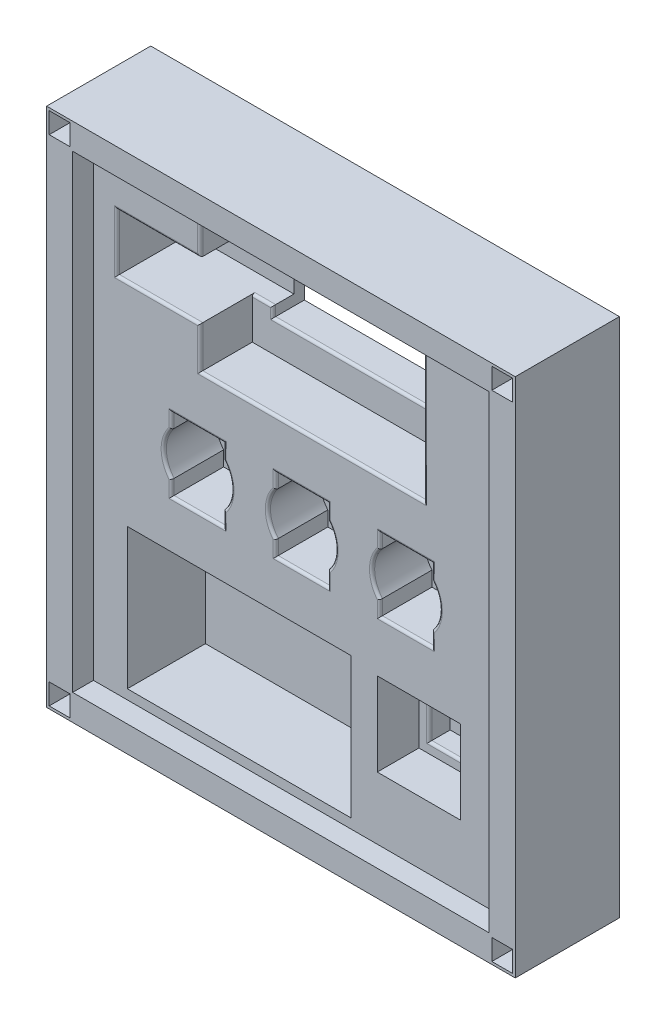
SolidWorks part; units mm, degrees
ref_plane "Front Plane" through (0, 0, 0) normal (0, 0, 1) x (1, 0, 0)
ref_plane "Top Plane" through (0, 0, 0) normal (0, 1, 0) x (1, 0, 0)
ref_plane "Right Plane" through (0, 0, 0) normal (1, 0, 0) x (0, 0, -1)
sketch "Sketch2" plane through (0, 0, 0) normal (0, 0, 1) x (1, 0, 0)
  line L1 (-45, 50) -> (45, 50)
  line L2 (-45, 50) -> (-45, -50)
  line L3 (-45, -50) -> (45, -50)
  line L4 (45, 50) -> (45, -50)
  line L5 (-45, 50) -> (45, -50) construction
  line L6 (-45, -50) -> (45, 50) construction
  point P0 (0, 0)
  dimension "D1" = 90
  dimension "D2" = 100
extrude "Boss-Extrude1" add sketch "Sketch2" along normal blind 50 contours L2 L1 L4 L3
sketch "Sketch4" plane through (0, 0, 0) normal (0, 0, -1) x (-1, 0, 0)
  line L0 (-45, 50) -> (45, 50)
  line L1 (45, 50) -> (45, -50)
  line L2 (45, -50) -> (-45, -50)
  line L3 (-45, -50) -> (-45, 50)
  line L4 (0, 0) -> (0, 30)
  line L5 (0, 0) -> (45, 0)
  line L6 (45, 0) -> (-45, 0)
  line L7 (0, 0) -> (0, -50)
  line L8 (0, -50) -> (0, -25)
  line L9 (0, -25) -> (0, 0)
  line L10 (0, 0) -> (0, 30)
  line L11 (-15.5, 22.5) -> (-23.5, 22.5)
  line L12 (-15.5, 37.5) -> (15.5, 37.5)
  line L13 (-15.5, 37.5) -> (-15.5, 22.5)
  line L14 (-15.5, 22.5) -> (15.5, 22.5)
  line L15 (15.5, 37.5) -> (15.5, 22.5)
  line L16 (-15.5, 37.5) -> (15.5, 22.5) construction
  line L17 (-15.5, 22.5) -> (15.5, 37.5) construction
  line L18 (-23.5, 22.5) -> (-23.5, 16.5)
  line L19 (-23.5, 16.5) -> (19.5, 16.5)
  line L20 (19.5, 16.5) -> (19.5, 41.5)
  line L21 (19.5, 41.5) -> (-23.5, 41.5)
  line L22 (-23.5, 41.5) -> (-23.5, 22.5)
  line L23 (15.5, 30) -> (15.5, 35.5)
  line L24 (15.5, 35.5) -> (35.5, 35.5)
  line L25 (35.5, 35.5) -> (35.5, 24.5)
  line L26 (35.5, 24.5) -> (15.5, 24.5)
  line L27 (0, 0) -> (20, 0)
  line L28 (0, 0) -> (-20, 0)
  line L34 (22.5, -25) -> (22.5, -22)
  line L35 (22.5, -22) -> (32.5, -22)
  line L39 (0, 0) -> (5, 0)
  line L40 (5, 0) -> (5, -7)
  line L41 (5, -7) -> (-5, -7)
  line L42 (-5, -7) -> (-5, 7)
  line L43 (-5, 7) -> (5, 7)
  line L44 (5, 7) -> (5, 0)
  line L45 (-20, 0) -> (-15, 0)
  line L46 (-15, 0) -> (-15, 7)
  line L47 (-15, 7) -> (-25, 7)
  line L48 (-25, 7) -> (-25, -7)
  line L49 (-25, -7) -> (-15, -7)
  line L50 (-15, -7) -> (-15, 0)
  line L51 (15, -7) -> (15, 0)
  line L52 (25, -7) -> (15, -7)
  line L53 (25, 7) -> (25, -7)
  line L54 (15, 7) -> (25, 7)
  line L55 (15, 0) -> (15, 7)
  line L56 (0, 0) -> (0, 15)
  line L57 (0, 15) -> (0, 7.5)
  line L58 (-45, -25) -> (45, -25)
  line L59 (0, -25) -> (22.5, -25)
  line L60 (0, -25) -> (-22.5, -25)
  line L61 (-22.5, -25) -> (-11.25, -25)
  line L62 (32.5, -22) -> (32.5, -28)
  line L63 (-16.5, -31) -> (-28.5, -31)
  line L64 (-28.5, -19) -> (-28.5, -31)
  line L65 (-16.5, -19) -> (-28.5, -19)
  line L66 (-16.5, -19) -> (-16.5, -31)
  line L67 (-14.5, -17) -> (-30.5, -17)
  line L68 (-30.5, -17) -> (-30.5, -33)
  line L69 (-14.5, -33) -> (-30.5, -33)
  line L70 (-14.5, -17) -> (-14.5, -33)
  line L71 (32.5, -28) -> (12.5, -28)
  line L72 (12.5, -28) -> (12.5, -22)
  line L73 (12.5, -22) -> (22.5, -22)
  line L74 (32.5, -25) -> (32.5, -17.1471)
  line L75 (32.5, -17.1471) -> (32.5, -42.1471)
  line L76 (32.5, -42.1471) -> (1.5, -42.1471)
  line L77 (1.5, -42.1471) -> (1.5, -17.1471)
  line L78 (1.5, -17.1471) -> (32.5, -17.1471)
  line L79 (33.5, -16.1471) -> (33.5, -43.1471)
  line L80 (33.5, -43.1471) -> (0.5, -43.1471)
  line L81 (0.5, -43.1471) -> (0.5, -16.1471)
  line L82 (0.5, -16.1471) -> (33.5, -16.1471)
  circle A0 centre (0, 0) radius 3.25
  circle A1 centre (-20, 0) radius 3.25
  circle A2 centre (20, 0) radius 3.25
  circle A4 centre (-22.5, -25) radius 4.5
  dimension "D3" = 1
  dimension "D1" = 15
  dimension "D2" = 31
  dimension "D6" = 30
  dimension "D7" = 0
  dimension "D8" = 25
  dimension "D9" = 22.5
sketch "Sketch5" plane through (0, 0, 50) normal (0, 0, 1) x (1, 0, 0)
  line L0 (-45, 50) -> (45, 50)
  line L1 (45, 50) -> (45, -50)
  line L2 (45, -50) -> (-45, -50)
  line L3 (-45, -50) -> (-45, 50)
  line L4 (-40, -45) -> (-40, 45)
  line L5 (-40, 45) -> (40, 45)
  line L6 (40, 45) -> (40, -45)
  line L7 (40, -45) -> (-40, -45)
  line L100 (-15.5, 37.5) -> (-15.5, 22.5)
  line L101 (-15.5, 22.5) -> (15.5, 22.5)
  line L102 (15.5, 22.5) -> (15.5, 37.5)
  line L103 (15.5, 37.5) -> (-15.5, 37.5)
  line L104 (-12.5, -22) -> (-32.5, -22)
  line L105 (-32.5, -22) -> (-32.5, -28)
  line L106 (-32.5, -28) -> (-12.5, -28)
  line L107 (-12.5, -28) -> (-12.5, -22)
  line L108 (-19.5, 41.5) -> (23.5, 41.5)
  line L109 (23.5, 41.5) -> (23.5, 16.5)
  line L110 (23.5, 16.5) -> (-19.5, 16.5)
  line L111 (-19.5, 16.5) -> (-19.5, 41.5)
  line L112 (-35.5, 35.5) -> (-15.5, 35.5)
  line L113 (-15.5, 35.5) -> (-15.5, 24.5)
  line L114 (-15.5, 24.5) -> (-35.5, 24.5)
  line L115 (-35.5, 24.5) -> (-35.5, 35.5)
  line L116 (-25, 7) -> (-15, 7)
  line L117 (-15, 7) -> (-15, -7)
  line L118 (-15, -7) -> (-25, -7)
  line L119 (-25, -7) -> (-25, 7)
  line L120 (-5, 7) -> (5, 7)
  line L121 (5, 7) -> (5, -7)
  line L122 (5, -7) -> (-5, -7)
  line L123 (-5, -7) -> (-5, 7)
  line L124 (15, 7) -> (25, 7)
  line L125 (25, 7) -> (25, -7)
  line L126 (25, -7) -> (15, -7)
  line L127 (15, -7) -> (15, 7)
  line L128 (-33.5, -16.1471) -> (-0.5, -16.1471)
  line L129 (-0.5, -16.1471) -> (-0.5, -43.1471)
  line L130 (-0.5, -43.1471) -> (-33.5, -43.1471)
  line L131 (-33.5, -43.1471) -> (-33.5, -16.1471)
  line L132 (16.5, -19) -> (28.5, -19)
  line L133 (28.5, -19) -> (28.5, -31)
  line L134 (28.5, -31) -> (16.5, -31)
  line L135 (16.5, -31) -> (16.5, -19)
  line L136 (14.5, -33) -> (14.5, -17)
  line L137 (14.5, -17) -> (30.5, -17)
  line L138 (30.5, -17) -> (30.5, -33)
  line L139 (30.5, -33) -> (14.5, -33)
  circle A40 centre (-20, 0) radius 3.25
  circle A41 centre (0, 0) radius 3.25
  circle A42 centre (20, 0) radius 3.25
  circle A43 centre (22.5, -25) radius 4.5
  circle A44 centre (-20, 0) radius 6.5
  circle A45 centre (0, 0) radius 6.5
  circle A46 centre (20, 0) radius 6.5
  line M9 (-45, -50) -> (45, -50)
  line M10 (45, -50) -> (45, 50)
  line M11 (45, 50) -> (-45, 50)
  line M12 (-45, 50) -> (-45, -50)
  dimension "D1" = 5
extrude "Cut-Extrude1" cut sketch "Sketch5" against normal blind 50 contours L102 L103 L100 L101 | A40 | A41 | L106 L107 L104 L105 | A42 | A43 region at (0, 30, 50) region at (-22.5, -25, 50) region at (-20, 0, 50) region at (0, 0, 50) region at (20, 0, 50) region at (22.5, -25, 50)
extrude "Cut-Extrude2" cut sketch "Sketch5<3>" against normal blind 44 contours L111 L110 L109 L108 L103 L102 L101 L100 region at (-15.9974, 36.5, 50)
sketch "Sketch5<3>" plane through (0, 0, 50) normal (0, 0, 1) x (1, 0, 0) same geometry as "Sketch5"
extrude "Cut-Extrude3" cut sketch "Sketch5<4>" against normal blind 48 contours L115 L114 L111 L112 | L114 L100 L112 L111 region at (-17.5, 30, 50) region at (-27.5, 30, 50)
sketch "Sketch5<4>" plane through (0, 0, 50) normal (0, 0, 1) x (1, 0, 0) same geometry as "Sketch5"
extrude "Cut-Extrude4" cut sketch "Sketch5<5>" against normal blind 44 contours L119 L118 L117 L116 A40 | L123 L122 L121 L120 A41 | L127 L126 L125 L124 A42 | L119 A44 | L117 A44 | L123 A45 | L121 A45 | L127 A46 | L125 A46 | A44 L117 L116 L119 | A44 L119 L118 L117 | A45 L123 L122 L121 | A45 L121 L120 L123 | A46 L125 L124 L127 | A46 L127 L126 L125 region at (-20, 6.896, 50) region at (-20, 6.336, 50) region at (-25.6064, 0, 50) region at (-14.3936, 0, 50) region at (-20, -6.604, 50) region at (0, 6.896, 50) region at (0, 6.336, 50) region at (-5.6064, 0, 50) region at (5.6064, 0, 50) region at (0, -6.604, 50) region at (20, 6.896, 50) region at (20, 6.336, 50) region at (14.3936, 0, 50) region at (25.6064, 0, 50) region at (20, -6.604, 50)
sketch "Sketch5<5>" plane through (0, 0, 50) normal (0, 0, 1) x (1, 0, 0) same geometry as "Sketch5"
extrude "Cut-Extrude5" cut sketch "Sketch5<6>" against normal blind 46 contours L135 L134 L133 L132 A43 region at (22.5, -19.1697, 50)
sketch "Sketch5<6>" plane through (0, 0, 50) normal (0, 0, 1) x (1, 0, 0) same geometry as "Sketch5"
extrude "Cut-Extrude6" cut sketch "Sketch5<7>" against normal blind 42 contours L139 L138 L137 L136 L134 L135 L132 L133 region at (14.7263, -25, 50)
sketch "Sketch5<7>" plane through (0, 0, 50) normal (0, 0, 1) x (1, 0, 0) same geometry as "Sketch5"
extrude "Cut-Extrude9" cut sketch "Sketch5<10>" against normal blind 49 contours L131 L130 L129 L128 L107 L106 L105 L104 region at (-16.144, -30.3703, 50)
sketch "Sketch5<10>" plane through (0, 0, 50) normal (0, 0, 1) x (1, 0, 0) same geometry as "Sketch5"
extrude "Cut-Extrude10" cut sketch "Sketch5<11>" against normal blind 34 contours L7 L6 L5 L4 A46 L127 L124 L125 L126 A45 L123 L120 L121 L122 A44 L119 L116 L117 L118 L130 L131 L128 L129 L114 L115 L112 L111 L108 L109 L110 L138 L139 L136 L137 region at (-38.7958, 0, 50)
sketch "Sketch5<11>" plane through (0, 0, 50) normal (0, 0, 1) x (1, 0, 0) same geometry as "Sketch5"
sketch "Sketch6" plane through (0, 0, 16) normal (0, 0, 1) x (1, 0, 0)
  line L0 (-0.5, -16.1471) -> (4.5, -16.1471)
  line L1 (4.5, -16.1471) -> (9.5, -16.1471)
  line L2 (9.5, -16.1471) -> (9.5, -43.1471)
  line L3 (9.5, -43.1471) -> (-0.5, -43.1471)
  line L4 (-0.5, -43.1471) -> (-0.5, -16.1471)
extrude "Cut-Extrude11" cut sketch "Sketch6" against normal blind 14
fillet "Fillet1" radius 0.5 7 edges at (-17.5, 24.5, 6) (-15.5, 23.5, 6) (0, 22.5, 6) (15.5, 30, 6) (0, 37.5, 6) (-17.5, 35.5, 6) (-15.5, 36.5, 6)
fillet "Fillet2" radius 0.5 24 edges at (13.5, 0, 16) (15, -5.5767, 16) (20, -7, 16) (25, -5.5767, 16) (26.5, 0, 16) (25, 5.5767, 16) (20, 7, 16) (15, 5.5767, 16) (5, -5.5767, 16) (6.5, 0, 16) (5, 5.5767, 16) (0, 7, 16) (0, -7, 16) (-5, -5.5767, 16) (-5, 5.5767, 16) (-6.5, 0, 16) (-26.5, 0, 16) (-25, -5.5767, 16) (-20, -7, 16) (-15, -5.5767, 16) (-13.5, 0, 16) (-15, 5.5767, 16) (-20, 7, 16) (-25, 5.5767, 16)
fillet "Fillet3" radius 0.5 4 edges at (22.5, -31, 8) (16.5, -25, 8) (22.5, -19, 8) (28.5, -25, 8)
fillet "Fillet4" radius 0.5 8 edges at (-27.5, 24.5, 16) (-35.5, 30, 16) (-27.5, 35.5, 16) (-19.5, 38.5, 16) (-19.5, 20.5, 16) (2, 16.5, 16) (23.5, 29, 16) (2, 41.5, 16)
sketch "Sketch7" plane through (0, -45, 0) normal (0, 1, 0) x (1, 0, 0)
  line L0 (0, -50) -> (0, -16)
  line L1 (40, -50) -> (-40, -50) construction
  line L2 (40, -16) -> (-40, -16) construction
  line L3 (0, -50) -> (0, -30)
extrude "Cut-Extrude12" cut sketch "Sketch5<12>" against normal blind 30 contours L6 L7 L4 L5 M12 M9 M10 M11 region at (0, 48.6546, 50)
sketch "Sketch5<12>" plane through (0, 0, 50) normal (0, 0, 1) x (1, 0, 0) same geometry as "Sketch5"
sketch "Sketch8" plane through (0, 0, 20) normal (0, 0, 1) x (1, 0, 0)
  line L0 (0, 50) -> (0, 45)
  line L1 (45, 50) -> (-45, 50) construction
  line L2 (-40, 45) -> (40, 45) construction
  line L3 (-40, 45) -> (-45, 45)
  line L4 (-45, 50) -> (-45, -50) construction
  line L5 (-45, 45) -> (-45, 50)
  line L6 (-45, 50) -> (-40, 50)
  line L7 (-40, 50) -> (-40, 45)
  line L8 (-40, -45) -> (-45, -45)
  line L9 (-45, -45) -> (-45, -50)
  line L10 (-45, -50) -> (-40, -50)
  line L11 (-45, -50) -> (45, -50) construction
  line L12 (-40, -50) -> (-40, -45)
  line L13 (-40, -50) -> (-41, -50)
  line L14 (-40, -50) -> (-40, -49)
  line L15 (-42.5, -45) -> (-42.5, -47.5)
  line L16 (-40, 45) -> (-41, 45)
  line L17 (-44.5, -45.5) -> (-40.5, -45.5)
  line L18 (-44.5, -45.5) -> (-44.5, -49.5)
  line L19 (-44.5, -49.5) -> (-40.5, -49.5)
  line L20 (-40.5, -45.5) -> (-40.5, -49.5)
  line L21 (-44.5, -45.5) -> (-40.5, -49.5) construction
  line L22 (-44.5, -49.5) -> (-40.5, -45.5) construction
  line L23 (-40, 45) -> (-40, 46)
  line L24 (-42.5, 50) -> (-42.5, 47.5)
  line L25 (44.5, -49.5) -> (40.5, -45.5) construction
  line L26 (-44.5, 49.5) -> (-40.5, 49.5)
  line L27 (-44.5, 49.5) -> (-44.5, 45.5)
  line L28 (-44.5, 45.5) -> (-40.5, 45.5)
  line L29 (-40.5, 49.5) -> (-40.5, 45.5)
  line L30 (-44.5, 49.5) -> (-40.5, 45.5) construction
  line L31 (-44.5, 45.5) -> (-40.5, 49.5) construction
  line L32 (44.5, -45.5) -> (40.5, -49.5) construction
  line L33 (40.5, -45.5) -> (40.5, -49.5)
  line L34 (44.5, -49.5) -> (40.5, -49.5)
  line L35 (44.5, -45.5) -> (44.5, -49.5)
  line L36 (44.5, -45.5) -> (40.5, -45.5)
  line L37 (42.5, -45) -> (42.5, -47.5)
  line L38 (40, -50) -> (40, -49)
  line L39 (40, -50) -> (41, -50)
  line L40 (40, -50) -> (40, -45)
  line L41 (45, -50) -> (40, -50)
  line L42 (45, -45) -> (45, -50)
  line L43 (40, -45) -> (45, -45)
  line L44 (44.5, 45.5) -> (40.5, 49.5) construction
  line L45 (44.5, 49.5) -> (40.5, 45.5) construction
  line L46 (40.5, 49.5) -> (40.5, 45.5)
  line L47 (44.5, 45.5) -> (40.5, 45.5)
  line L48 (44.5, 49.5) -> (44.5, 45.5)
  line L49 (44.5, 49.5) -> (40.5, 49.5)
  line L50 (42.5, 50) -> (42.5, 47.5)
  line L51 (40, 45) -> (40, 46)
  line L52 (40, 45) -> (41, 45)
  line L53 (40, 50) -> (40, 45)
  line L54 (45, 50) -> (40, 50)
  line L55 (45, 45) -> (45, 50)
  line L56 (40, 45) -> (45, 45)
extrude "Cut-Extrude13" cut sketch "Sketch8" against normal blind 5 contours L29 L26 L27 L28 | L48 L49 L46 L47 | L35 L36 L33 L34 | L20 L17 L18 L19 region at (-41.5, 49.4434, 20) region at (-41.5, -45.5566, 20) region at (41.5, -45.5566, 20) region at (41.5, 49.4434, 20)
